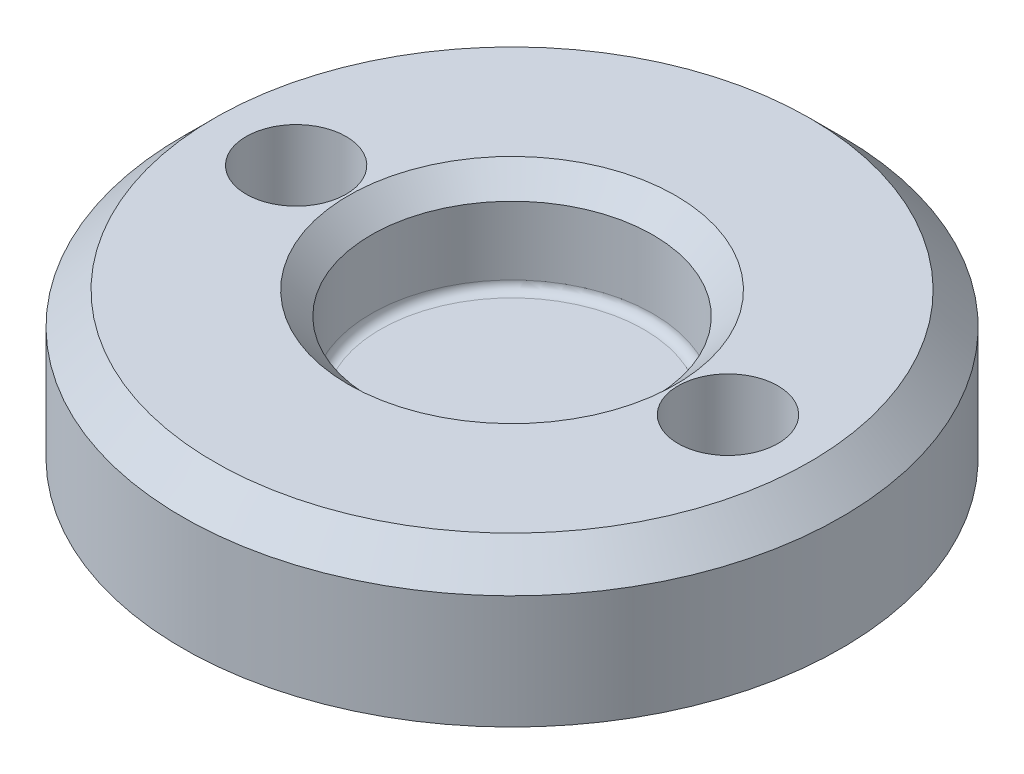
SolidWorks part; units mm, degrees
material "Brass"
ref_plane "Front Plane" through (0, 0, 0) normal (0, 0, 1) x (1, 0, 0)
ref_plane "Top Plane" through (0, 0, 0) normal (0, 1, 0) x (1, 0, 0)
ref_plane "Right Plane" through (0, 0, 0) normal (1, 0, 0) x (0, 0, -1)
sketch "Sketch1" plane through (0, 0, 0) normal (0, 0, 1) x (1, 0, 0)
  line L0 (0, 0) -> (0, 7.0462) construction
  line L1 (0, 0) -> (-7.25, 0)
  line L2 (-7.25, 0) -> (-7.25, 3.2)
  line L3 (-7.25, 3.2) -> (-3.1, 3.2)
  line L4 (-3.1, 3.2) -> (-3.1, 1)
  line L5 (-3.1, 1) -> (0, 1)
  line L6 (0, 0) -> (0, 1)
  dimension "D1" = 3.1
  dimension "D2" = 4.15
  dimension "D3" = 1
  dimension "D4" = 2.2
  dimension "D5" = 7.25
revolve "Revolve1" add sketch "Sketch1" angle 360 about L0
chamfer "Chamfer2" distance 0.5 angle 45 1 edges at (0, 3.2, -3.1)
sketch "Sketch2" plane through (0, 3.2, 0) normal (0, 1, 0) x (1, 0, 0)
  line L0 (-6.8053, -2.5) -> (-12.25, -2.5)
  line L1 (-12.25, -2.5) -> (-12.25, 2.5)
  line L2 (-12.25, 2.5) -> (-6.8053, 2.5)
  line L3 (-12.25, 0) -> (-7.25, 0) construction
  circle A0 centre (0, 0) radius 7.25 construction
  arc A1 (-6.8053, 2.5) -> (-6.8053, -2.5) centre (0, 0) ccw
  point P2 (-12.25, 0)
  dimension "D1" = 5
extrude "Boss-Extrude1" [suppressed] add sketch "Sketch2" against normal up to surface (3 mm away) up to face at (0, 0, -7.25)
hole_wizard "CSK for M2 Flat Head Machine Screw1" positions "Sketch3" profile "Sketch4" countersink size "M2" standard "ANSI Metric"
sketch "Sketch3" plane through (0, 0, 0) normal (0, -1, 0) x (-1, 0, 0)
  point P0 (4.75, 0)
  dimension "D1" = 4.75
sketch "Sketch4" plane through (-4.75, 0, 0) normal (1, 0, 0) x (0, 0, -1)
  line L0 (0, 0) -> (0, 5.6609)
  line L1 (0, 5.6609) -> (1.1, 5)
  line L2 (1.1, 5) -> (1.1, 1.1)
  line L3 (1.1, 1.1) -> (2.2, 0)
  line L5 (2.2, 0) -> (0, 0)
  line L6 (-1.1, 1.1) -> (-2.2, 0) construction
  line L10 (0, 5.6609) -> (-1.1, 5) construction
  line L11 (0, -6.35) -> (0, 107.95) construction
  dimension "Hole Dia." = 2.2
  dimension "Hole Depth" = 5
  dimension "Near C'Sink Dia." = 4.4
  dimension "Near C'Sink Angle" = 90
  dimension "Drill Angle" = 118
sketch "Sketch5" [suppressed] plane through (0, 0, 0) normal (0, -1, 0) x (1, 0, 0)
  line L1 (-6.8053, 2.5) -> (-12.25, 2.5) construction
  line L2 (-6.8053, 2.5) -> (-12.25, 2.5) construction
  line L3 (-12.25, -2.5) -> (-6.8053, -2.5) construction
  line L4 (-4.75, -2.5) -> (-12.25, -2.5)
  line L5 (-12.25, -2.5) -> (-12.25, 2.5)
  line L9 (-12.25, 2.5) -> (-4.75, 2.5)
  arc A0 (-4.75, -2.5) -> (-4.75, 2.5) centre (-4.75, 0) cw
extrude "Cut-Extrude1" [suppressed] cut sketch "Sketch5" against normal through all both and the other way through all
pattern_circular "CirPattern1" count 2 over 360 about axis through (0, 0, 0) along (0, -1, 0) of "CSK for M2 Flat Head Machine Screw1", "Boss-Extrude1", "Cut-Extrude1" reverse direction yes
fillet "Fillet1" [suppressed] radius 10
chamfer "Chamfer3" distance 0.7 angle 45 1 edges at (0, 3.2, -7.25)
fillet "Fillet2" radius 0.2 1 edges at (0, 1, -3.1)
